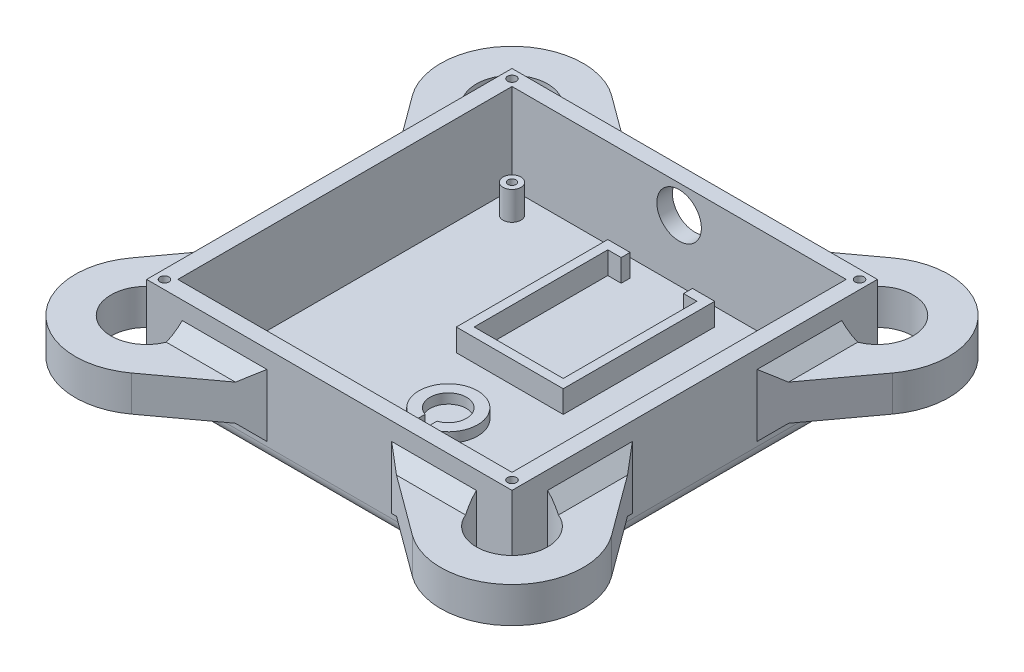
SolidWorks part; units mm, degrees
ref_plane "Front Plane" through (0, 0, 0) normal (0, 0, 1) x (1, 0, 0)
ref_plane "Top Plane" through (0, 0, 0) normal (0, 1, 0) x (1, 0, 0)
ref_plane "Right Plane" through (0, 0, 0) normal (1, 0, 0) x (0, 0, -1)
sketch "Sketch1" plane through (0, 0, 0) normal (0, 1, 0) x (1, 0, 0)
  line L0 (0, 41) -> (0, -41) construction
  line L2 (-37.5, 37.5) -> (37.5, 37.5)
  line L3 (37.5, 37.5) -> (37.5, -37.5)
  line L5 (-37.5, -37.5) -> (37.5, -37.5)
  line L6 (-37.5, 37.5) -> (-37.5, -37.5)
  line L7 (-41, 0) -> (41, 0) construction
  line L8 (41, 41) -> (-41, 41)
  line L9 (-41, 41) -> (-41, -41)
  line L11 (41, 41) -> (41, -41)
  line L12 (41, -41) -> (-41, -41)
  point P2 (37.5, 0)
  point P4 (0, 37.5)
  point P7 (0, 0)
  point P14 (0, 0)
  dimension "D1" = 75
  dimension "D2" = 82
  dimension "D3" = 82
  dimension "D4" = 75
extrude "Boss-Extrude1" add sketch "Sketch1" along normal blind 20 contours L6 L2 L3 L5 L12 L11 L8 L9 region at (39.8403, 0, 0)
sketch "Sketch2" plane through (0, 0, 0) normal (0, -1, 0) x (1, 0, 0)
  line L1 (-41, 41) -> (41, 41)
  line L2 (-41, 41) -> (-41, -41)
  line L3 (-41, -41) -> (41, -41)
  line L4 (41, 41) -> (41, -41)
extrude "Boss-Extrude2" add sketch "Sketch2" along normal blind 2
sketch "Sketch3" plane through (0, 0, 0) normal (0, 1, 0) x (1, 0, 0)
  line L0 (0, 37.5) -> (0, -37.5) construction
  line L1 (-37.5, 37.5) -> (37.5, 37.5) construction
  line L2 (-37.5, -37.5) -> (37.5, -37.5) construction
  line L3 (0, -37.5) -> (0, 0) construction
  line L4 (0, 0) -> (37.5, 0) construction
  line L5 (37.5, 37.5) -> (37.5, -37.5) construction
  line L6 (37.5, 0) -> (-37.5, 0) construction
  line L7 (-37.5, 37.5) -> (-37.5, -37.5) construction
  line L8 (-30, 34.5) -> (30, 34.5) construction
  line L9 (30, 34.5) -> (30, -34.5) construction
  line L10 (-30, -34.5) -> (30, -34.5) construction
  line L11 (-30, 34.5) -> (-30, -34.5) construction
  line L14 (-37.5, 37.5) -> (37.5, 37.5) construction
  circle A0 centre (32.5, 32.5) radius 2
  circle A1 centre (32.5, 32.5) radius 0.9
  circle A2 centre (32.5, -32.5) radius 2
  circle A3 centre (32.5, -32.5) radius 0.9
  circle A4 centre (-32.5, -32.5) radius 0.9
  circle A5 centre (-32.5, -32.5) radius 2
  circle A6 centre (-32.5, 32.5) radius 2
  circle A7 centre (-32.5, 32.5) radius 0.9
  point P23 (30, 0)
  point P28 (0, -34.5)
  point P32 (0, 34.5)
  dimension "D3" = 2
  dimension "D4" = 4
  dimension "D1" = 5
  dimension "D2" = 5
extrude "Boss-Extrude3" add sketch "Sketch3" along normal blind 6.4
sketch "Sketch4" plane through (0, 20, 0) normal (0, 1, 0) x (1, 0, 0)
  line L0 (0, 41) -> (0, -41) construction
  line L1 (-37.5, 37.5) -> (37.5, 37.5) construction
  line L2 (41, -41) -> (-41, -41) construction
  line L3 (-41, 0) -> (41, 0) construction
  line L4 (-41, 41) -> (-41, -41) construction
  line L5 (-41, 41) -> (-41, -41) construction
  line L6 (41, 41) -> (-41, 41) construction
  line L9 (41, 41) -> (41, -41) construction
  circle A1 centre (-39, 39) radius 1
  circle A2 centre (39, 39) radius 1
  circle A3 centre (39, -39) radius 1
  circle A4 centre (-39, -39) radius 1
  dimension "D1" = 3.5
  dimension "D2" = 2
  dimension "D3" = 2
extrude "Cut-Extrude1" cut sketch "Sketch4" against normal blind 8
ref_plane "Plane1" through (0, 5, 0) normal (0, -1, 0) x (-1, 0, 0)
sketch "Sketch10" plane through (0, 0, 0) normal (0, 1, 0) x (1, 0, 0)
  line L0 (0, 37.5) -> (0, -10.2) construction
  line L1 (-37.5, 37.5) -> (37.5, 37.5) construction
  line L4 (-37.5, 37.5) -> (-37.5, -37.5) construction
  line L5 (-37.5, 0) -> (37.5, 0) construction
  line L6 (37.5, 37.5) -> (37.5, -37.5) construction
  line L13 (-1.3349, -18.1766) -> (-1.3349, -20.7636)
  line L14 (1.3349, -18.1766) -> (1.3349, -20.7636)
  arc A0 (1.3349, -18.1766) -> (-1.3349, -18.1766) centre (0, -14.3) ccw
  arc A1 (1.3349, -20.7636) -> (-1.3349, -20.7636) centre (0, -14.3) ccw
  dimension "D2" = 8.2
  dimension "D1" = 13.2
  dimension "D3" = 14.3
extrude "Boss-Extrude7" add sketch "Sketch10" along normal blind 2.2
sketch "Sketch11" plane through (0, 0, 0) normal (0, 1, 0) x (1, 0, 0)
  line L0 (12, -1.3684) -> (37.5, 0) construction
  line L1 (-10, 31.5) -> (-10, 1.5)
  line L3 (-12, 33.5) -> (-12, -0.5)
  line L5 (37.5, 37.5) -> (37.5, -37.5) construction
  line L6 (-37.5, 37.5) -> (37.5, 37.5) construction
  line L7 (-10, 31.5) -> (-7, 31.5)
  line L9 (-10, 1.5) -> (10, 1.5)
  line L12 (-12, -0.5) -> (12, -0.5)
  line L13 (12, -0.5) -> (12, 33.5)
  line L14 (12, 33.5) -> (7, 33.5)
  line L15 (7, 33.5) -> (7, 31.5)
  line L16 (10, 31.5) -> (10, 1.5)
  line L17 (0, 1.5) -> (10, 1.5)
  line L19 (7, 31.5) -> (10, 31.5)
  line L21 (-12, 33.5) -> (-7, 33.5)
  line L22 (-7, 33.5) -> (-7, 31.5)
  line L23 (-7, 31.5) -> (-10, 31.5)
  line L24 (7, 31.5) -> (10, 31.5)
  dimension "D1" = 30
  dimension "D2" = 6
  dimension "D3" = 10
  dimension "D4" = 2
  dimension "D5" = 10
  dimension "D6" = 2
  dimension "D7" = 3
  dimension "D8" = 3
  dimension "D9" = 2
  dimension "D10" = 2
  dimension "D11" = 2
fillet "Fillet1" radius 3 4 edges at (0, -2, 41) (41, -2, 0) (0, -2, -41) (-41, -2, 0)
extrude "Boss-Extrude8" add sketch "Sketch11" along normal blind 5 contours L22 L21 L3 L12 L13 L14 L15 L19 L16 L9 L1 L7 region at (-10.4162, 0, -16.5)
sketch "Sketch15" plane through (0, 0, -41) normal (0, 0, -1) x (-1, 0, 0)
  line L1 (0, 20) -> (0, 1) construction
  line L3 (-41, 20) -> (41, 20) construction
  circle A1 centre (0, 13.7) radius 5
  dimension "D1" = 6.3
extrude "Cut-Extrude2" cut sketch "Sketch15" against normal up to surface (3.5 mm away) up to face at (0, 10, -37.5)
sketch "Sketch17" plane through (0, 5, 0) normal (0, -1, 0) x (-1, 0, 0)
  line L0 (41, 25) -> (41, 14)
  line L1 (25, 41) -> (41, 41) construction
  line L2 (41, 41) -> (41, 25) construction
  line L3 (25, 41) -> (33, 41)
  line L4 (41, 33) -> (41, 25)
  line L5 (14, 41) -> (31.5185, 53.888)
  line L6 (-41, 41) -> (41, 41) construction
  line L7 (53.888, 31.5185) -> (41, 14)
  line L8 (41, 41) -> (41, -41) construction
  line L9 (14, 41) -> (25, 41)
  line L10 (0, 0) -> (0, -38) construction
  line L11 (-38, -38) -> (38, -38) construction
  line L12 (0, -38) -> (0, 0) construction
  line L13 (0, 0) -> (38, 0) construction
  line L14 (38, -38) -> (38, 38) construction
  line L15 (-41, 33) -> (-41, 25)
  line L16 (-25, 41) -> (-33, 41)
  line L17 (-14, 41) -> (-25, 41)
  line L18 (-14, 41) -> (-31.5185, 53.888)
  line L19 (-53.888, 31.5185) -> (-41, 14)
  line L20 (-41, 25) -> (-41, 14)
  line L21 (41, -33) -> (41, -25)
  line L22 (25, -41) -> (33, -41)
  line L23 (14, -41) -> (25, -41)
  line L24 (14, -41) -> (31.5185, -53.888)
  line L25 (53.888, -31.5185) -> (41, -14)
  line L26 (41, -25) -> (41, -14)
  line L27 (-25, -41) -> (-33, -41)
  line L28 (-14, -41) -> (-25, -41)
  line L29 (-14, -41) -> (-31.5185, -53.888)
  line L30 (-53.888, -31.5185) -> (-41, -14)
  line L31 (-41, -25) -> (-41, -14)
  line L32 (-41, -33) -> (-41, -25)
  arc A2 (41, 33) -> (33, 41) centre (41, 41) ccw
  arc A3 (53.888, 31.5185) -> (31.5185, 53.888) centre (41, 41) ccw
  arc A4 (-41, 33) -> (-33, 41) centre (-41, 41) cw
  arc A5 (-53.888, 31.5185) -> (-31.5185, 53.888) centre (-41, 41) cw
  arc A6 (41, -33) -> (33, -41) centre (41, -41) cw
  arc A7 (53.888, -31.5185) -> (31.5185, -53.888) centre (41, -41) cw
  arc A8 (-41, -33) -> (-33, -41) centre (-41, -41) ccw
  arc A9 (-53.888, -31.5185) -> (-31.5185, -53.888) centre (-41, -41) ccw
  dimension "D1" = 16
  dimension "D2" = 8
  dimension "D3" = 11
  dimension "D4" = 11
  dimension "D5" = 8
  dimension "D6" = 8
extrude "Boss-Extrude9" add sketch "Sketch17" against normal blind 8
chamfer "Chamfer1" distance 3 angle 45 16 edges at (-41, 5, -23.5) (-41, 13, -23.5) (-23.5, 13, -41) (-23.5, 5, -41) (23.5, 5, -41) (23.5, 13, -41) (41, 5, -23.5) (41, 13, -23.5) (41, 13, 23.5) (41, 5, 23.5) (23.5, 5, 41) (23.5, 13, 41) (-23.5, 13, 41) (-23.5, 5, 41) (-41, 5, 23.5) (-41, 13, 23.5)
